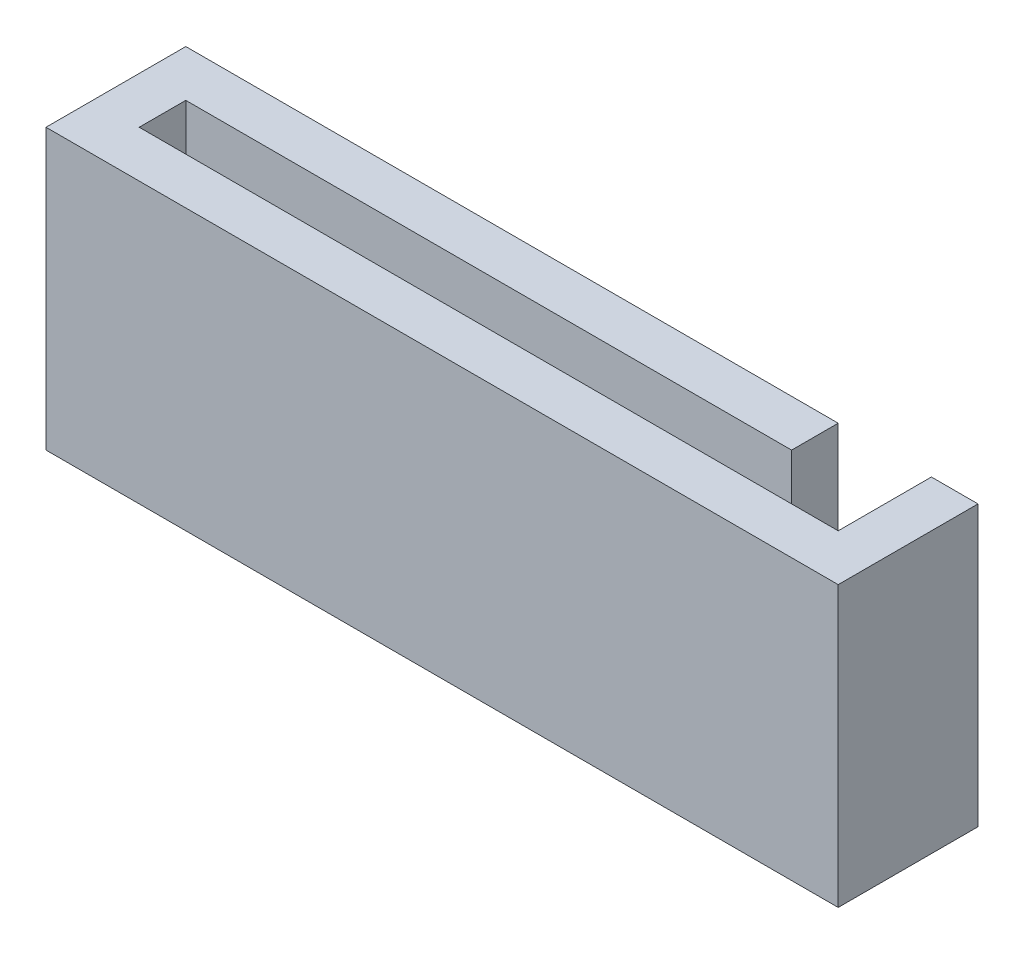
SolidWorks part; units mm, degrees
ref_plane "Front Plane" through (0, 0, 0) normal (0, 0, 1) x (1, 0, 0)
ref_plane "Top Plane" through (0, 0, 0) normal (0, 1, 0) x (1, 0, 0)
ref_plane "Right Plane" through (0, 0, 0) normal (1, 0, 0) x (0, 0, -1)
sketch "Sketch1" plane through (0, 0, 0) normal (0, 1, 0) x (1, 0, 0)
  line L0 (0, 0) -> (-17, 0)
  line L5 (-17, 0) -> (-17, 3)
  line L6 (-17, 3) -> (0, 3)
  line L7 (0, 3) -> (0, 0)
  line L8 (-16, 3) -> (-16, 0)
  line L9 (-1, 3) -> (-1, 0)
  line L10 (-16, 2) -> (-3, 2)
  line L11 (-16, 1) -> (-1, 1)
  line L12 (-3, 2) -> (-3, 3)
  point P0 (0, 0)
  dimension "D1" = 3
  dimension "D2" = 17
  dimension "D3" = 1
  dimension "D4" = 1
  dimension "D5" = 1
  dimension "D6" = 1
  dimension "D7" = 2
extrude "Boss-Extrude1" add sketch "Sketch1" along normal blind 6 contours L10 L12 L6 L8 | L8 L6 L5 L0 | L11 L8 L0 L9 | L6 L9 L0 L7 region at (-0.5, 0, -1.5) region at (-8.5, 0, -0.5) region at (-16.5, 0, -1.5) region at (-9.5, 0, -2.5)
extrude "Boss-Extrude2" add sketch "Sketch1<3>" along normal blind 1 contours L12 L10 L8 L11 L9 L6 region at (-7.7353, 0, -1.6176)
sketch "Sketch1<3>" plane through (0, 0, 0) normal (0, 1, 0) x (1, 0, 0) same geometry as "Sketch1"
